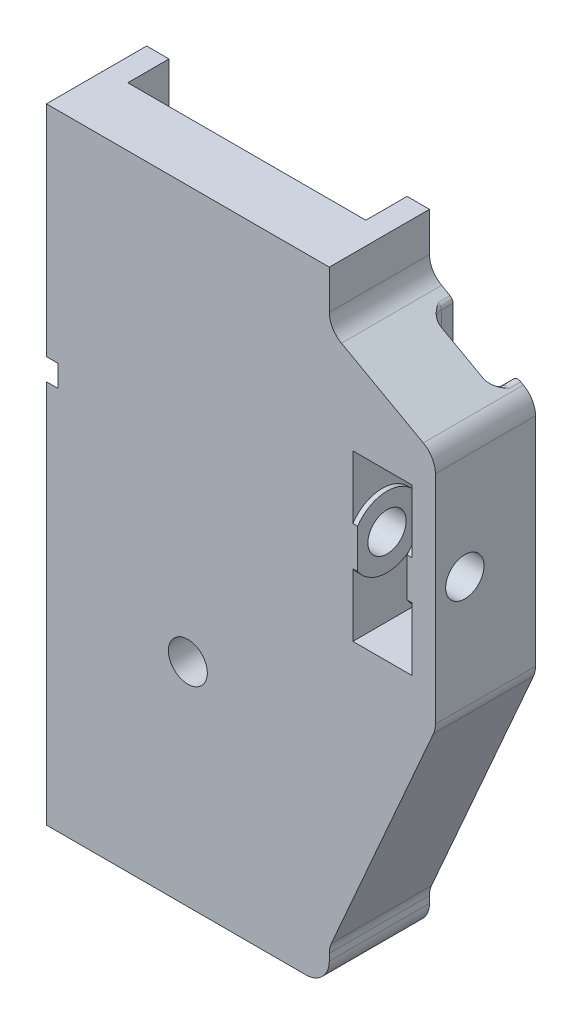
SolidWorks part; units mm, degrees
material "ABS"
ref_plane "前视基准面" through (0, 0, 0) normal (0, 0, 1) x (1, 0, 0)
ref_plane "上视基准面" through (0, 0, 0) normal (0, 1, 0) x (1, 0, 0)
ref_plane "右视基准面" through (0, 0, 0) normal (1, 0, 0) x (0, 0, -1)
other "Configuration Table"
sketch "草图1" plane through (0, 0, 0) normal (0, 0, 1) x (1, 0, 0)
  line L0 (0, 0) -> (0, 53)
  line L1 (0, 53) -> (24, 53)
  line L2 (24, 53) -> (24, 48.5)
  line L3 (24, 48.5) -> (33, 43.5)
  line L4 (33, 43.5) -> (33, 23.5)
  line L5 (33, 23.5) -> (24, 3)
  line L6 (24, 3) -> (24, 0)
  line L7 (24, 0) -> (0, 0)
  line L9 (26, 40.5) -> (31, 40.5)
  line L10 (26, 40.5) -> (26, 26.5)
  line L11 (26, 26.5) -> (31, 26.5)
  line L12 (31, 40.5) -> (31, 26.5)
  circle A0 centre (12, 18) radius 1.65
  dimension "D12" = 3.3
  dimension "D13" = 12
  dimension "D14" = 18
  dimension "D1" = 53
  dimension "D2" = 24
  dimension "D3" = 9
  dimension "D4" = 3
  dimension "D5" = 20
  dimension "D6" = 5
  dimension "D7" = 9.5
  dimension "D8" = 5
  dimension "D9" = 14
  dimension "D10" = 2
  dimension "D11" = 3
extrude "凸台-拉伸1" add sketch "草图1" along normal blind 8.5
sketch "草图2" plane through (0, 53, 0) normal (0, 1, 0) x (1, 0, 0)
  line L0 (24, 0) -> (0, 0) construction
  line L1 (1.9, 0) -> (22.1, 0)
  line L2 (1.9, 0) -> (1.9, -3.5)
  line L3 (1.9, -3.5) -> (22.1, -3.5)
  line L4 (22.1, 0) -> (22.1, -3.5)
  line L5 (0, -8.5) -> (0, 0) construction
  dimension "D1" = 3.5
  dimension "D2" = 1.9
  dimension "D3" = 20.2
extrude "切除-拉伸1" cut sketch "草图2" against normal offset from surface (50.1 mm away) 2.9 up to face at (12, 0, 4.25)
sketch "草图3" plane through (33, 0, 0) normal (1, 0, 0) x (0, 0, -1)
  line L0 (-8.5, 23.5) -> (-8.5, 43.5) construction
  circle A0 centre (-6, 33.5) radius 1.625
  dimension "D1" = 3.25
  dimension "D2" = 2.5
  dimension "D3" = 7
extrude "切除-拉伸2" cut sketch "草图3" against normal up to surface (7 mm away) up to face at (26, 33.5, 4.25)
sketch "草图4" plane through (26, 0, 0) normal (1, 0, 0) x (0, 0, -1)
  circle A0 centre (-6, 33.5) radius 1
  dimension "D1" = 2
extrude "切除-拉伸3" cut sketch "草图4" against normal up to surface (3.9 mm away) up to face at (22.1, 27.95, 1.75)
sketch "草图5" plane through (26, 0, 0) normal (1, 0, 0) x (0, 0, -1)
  line L0 (-8.5, 40.5) -> (-8.5, 26.5) construction
  line L1 (-8.5, 35.1583) -> (-8.5, 31.8417)
  circle A0 centre (-6, 33.5) radius 1 construction
  circle A1 centre (-6, 33.5) radius 1
  arc A2 (-8.5, 31.8417) -> (-8.5, 35.1583) centre (-6, 33.5) ccw
  dimension "D1" = 6
extrude "凸台-拉伸2" add sketch "草图5" along normal blind 0.4
sketch "草图6" plane through (31, 0, 0) normal (-1, 0, 0) x (0, 0, 1)
  line L1 (8.5, 31.8417) -> (8.5, 35.1583)
  line L2 (8.5, 31.8417) -> (8.5, 35.1583)
  circle A0 centre (6, 33.5) radius 1.625 construction
  arc A1 (8.5, 35.1583) -> (8.5, 31.8417) centre (6, 33.5) ccw
  arc A2 (8.5, 35.1583) -> (8.5, 31.8417) centre (6, 33.5) ccw
  circle A3 centre (6, 33.5) radius 1.625
  dimension "D1" = 0
extrude "凸台-拉伸3" add sketch "草图6" along normal blind 0.4
fillet "圆角1" radius 2 1 edges at (24, 3, 4.25)
fillet "圆角2" radius 2 4 edges at (24, 0, 4.25) (33, 23.5, 4.25) (33, 43.5, 4.25) (24, 48.5, 4.25)
sketch "草图7" plane through (33, 0, 0) normal (1, 0, 0) x (0, 0, -1)
  circle A0 centre (-6, 33.5) radius 1.625 construction
  circle A1 centre (-6, 33.5) radius 1.625
extrude "切除-拉伸4" cut sketch "草图7" against normal through all
sketch "草图8" plane through (0, 0, 0) normal (0, 0, -1) x (-1, 0, 0)
  line L1 (-31, 40.5) -> (-26, 40.5)
  line L2 (-31, 40.5) -> (-31, 49.5231)
  line L3 (-31, 49.5231) -> (-26, 49.5231)
  line L4 (-26, 40.5) -> (-26, 49.5231)
extrude "切除-拉伸5" cut sketch "草图8" against normal blind 2
fillet "圆角3" radius 0.5 2 edges at (31, 44.6111, 1) (26, 47.3889, 1)
fillet "圆角4" radius 1 4 edges at (25.9309, 47.3483, 2) (31.2464, 44.1923, 2) (26, 43.7973, 2) (31, 42.1307, 2)
sketch "Sketch1" plane through (0, 0, 0) normal (-1, 0, 0) x (0, 0, 1)
  line L1 (2.9689, 33.5) -> (4.4845, 30.875)
  line L2 (4.4845, 30.875) -> (7.5155, 30.875)
  line L3 (7.5155, 30.875) -> (9.0311, 33.5)
  line L4 (9.0311, 33.5) -> (7.5155, 36.125)
  line L5 (7.5155, 36.125) -> (4.4845, 36.125)
  line L6 (4.4845, 36.125) -> (2.9689, 33.5)
  circle A0 centre (6, 33.5) radius 2.625 construction
  dimension "D1" = 5.25
extrude "Cut-Extrude1" cut sketch "Sketch1" against normal blind 1
